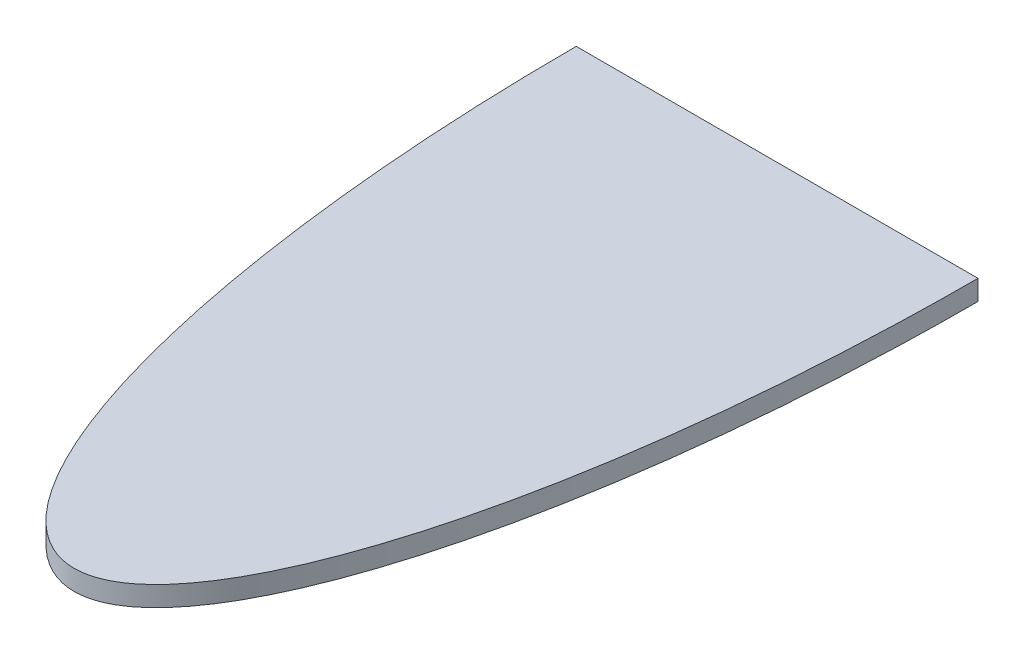
SolidWorks part; units mm, degrees
ref_plane "Front Plane" through (0, 0, 0) normal (0, 0, 1) x (1, 0, 0)
ref_plane "Top Plane" through (0, 0, 0) normal (0, 1, 0) x (1, 0, 0)
ref_plane "Right Plane" through (0, 0, 0) normal (1, 0, 0) x (0, 0, -1)
sketch "Sketch1" plane through (0, 0, 0) normal (0, 1, 0) x (1, 0, 0)
  line L0 (-25.4, 0) -> (25.4, 0)
  line L1 (0, 88.9) -> (0, -88.9) construction
  ellipse E0 centre (0, 0) end of major axis (0, 88.9) minor radius 25.4
  dimension "D1" = 50.8
  dimension "D2" = 177.8
extrude "Boss-Extrude1" add sketch "Sketch1" along normal blind 2.54 contours L0 L1 E0 | L1 L0 E0 region at (-10.7801, 0, 37.7303) region at (10.7801, 0, 37.7303)
